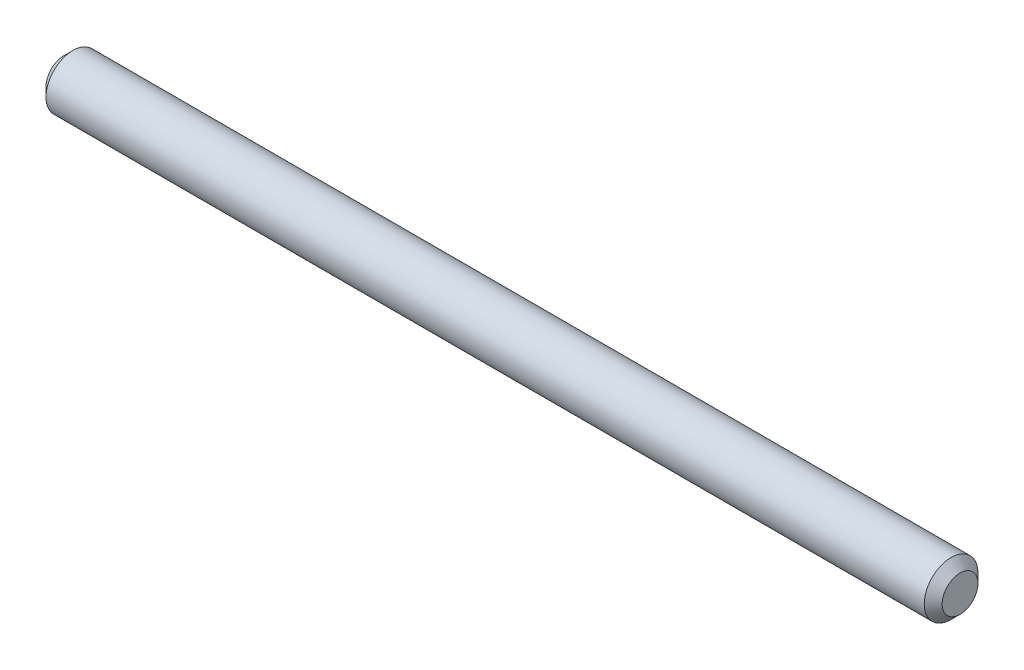
SolidWorks part; units mm, degrees
ref_plane "Front Plane" through (0, 0, 0) normal (0, 0, 1) x (1, 0, 0)
ref_plane "Top Plane" through (0, 0, 0) normal (0, 1, 0) x (1, 0, 0)
ref_plane "Right Plane" through (0, 0, 0) normal (1, 0, 0) x (0, 0, -1)
sketch "Sketch1" plane through (0, 0, 0) normal (0, 0, 1) x (1, 0, 0)
  line L0 (0, 0) -> (50, 0) construction
  line L1 (0, 0) -> (50, 0)
  line L2 (50, 0) -> (50, 1.5)
  line L3 (50, 1.5) -> (0, 1.5)
  line L4 (0, 1.5) -> (0, 0)
  dimension "L" = 50
  dimension "D" = 3
revolve "Revolve1" add sketch "Sketch1" angle 360 about L0
chamfer "Chamfer1" distance 0.5 angle 45 2 edges at (50, 0, 1.5) (0, 0, 1.5)
ref_plane "Plane1" through (0, 0, 1.5) normal (0, 0, 1) x (1, 0, 0)
ref_plane "Plane2" through (50, 0, 0) normal (1, 0, 0) x (0, 0, -1)
other "DeleteFace1" [suppressed]
chamfer "Chamfer2" [suppressed] distance 2 angle 45
ref_plane "Dim. KC" [suppressed] through (2, 0, 0) normal (1, 0, 0) x (0, 0, -1)
ref_plane "Plane3" [suppressed] through (2, 0, 0) normal (1, 0, 0) x (0, 0, -1)
ref_plane "Plane4" [suppressed] through (8, 0, 0) normal (1, 0, 0) x (0, 0, -1)
sketch "Sketch2" [suppressed] plane through (0, 0, 4) normal (0, 0, 1) x (1, 0, 0)
  line L0 (2, 0) -> (8, 0) construction
  line L1 (2, 1.5) -> (8, 1.5)
  line L2 (2, 1.5) -> (2, -1.5) construction
  line L3 (2, -1.5) -> (8, -1.5)
  line L4 (8, 1.5) -> (8, -1.5) construction
  line L5 (5, 1.5) -> (5, -1.5) construction
  line L6 (2, -4.4) -> (2, 4.4) construction
  line L7 (8, 1.5) -> (8, -1.5)
  line L8 (8, -4.4) -> (8, 4.4) construction
  line L9 (2, 1.5) -> (2, -1.5)
  line L12 (2, -4.4) -> (2, 4.4) construction
  dimension "A" = 6
  dimension "B_s" = 3
extrude "Boss-Extrude1" [suppressed] add sketch "Sketch2" against normal blind 1.8 separate body
fillet "Fillet1" [suppressed] type full round
fillet "Fillet2" [suppressed] type full round
sketch "Sketch3" [suppressed] plane through (0, 0, 4) normal (0, 0, 1) x (1, 0, 0)
  line L0 (9, 1.5) -> (9, -1.5) construction
  line L1 (6.5, 1.5) -> (11.5, 1.5)
  line L2 (6.5, 1.5) -> (6.5, -1.5)
  line L3 (6.5, -1.5) -> (11.5, -1.5)
  line L4 (11.5, 1.5) -> (11.5, -1.5)
  line L7 (6.5, 0) -> (11.5, 0) construction
  line L9 (10, 1.5) -> (10, -1.5) construction
  line L10 (8, 1.5) -> (8, -1.5) construction
  line L11 (2, 1.5) -> (8, 1.5) construction
  line L12 (2, -1.5) -> (8, -1.5) construction
  dimension "D1" = 1.5
  dimension "D2" = 2
  dimension "D3" = 1.5
extrude "Boss-Extrude2" [suppressed] add sketch "Sketch3" against normal blind 1.8
fillet "Fillet3" [suppressed] radius 0.1
other "DeleteFace2" [suppressed]
other "DeleteFace3" [suppressed]
combine bodies "Combine1" [suppressed] operation type subtract main body 101 bodies to subtract 146
ref_plane "KC_SEC1" [suppressed] through (5, 0, 0) normal (1, 0, 0) x (0, 0, -1)
ref_plane "KC_SEC2" [suppressed] through (9, 0, 0) normal (1, 0, 0) x (0, 0, -1)
ref_plane "Dim. WKC" [suppressed] through (2, 0, 0) normal (1, 0, 0) x (0, 0, -1)
ref_plane "Dim. K" [suppressed] through (20, 0, 0) normal (1, 0, 0) x (0, 0, -1)
ref_plane "Plane5" [suppressed] through (2, 0, 0) normal (1, 0, 0) x (0, 0, -1)
ref_plane "Plane6" [suppressed] through (20, 0, 0) normal (1, 0, 0) x (0, 0, -1)
sketch "Sketch4" [suppressed] plane through (0, 0, 4) normal (0, 0, 1) x (1, 0, 0)
  line L0 (2, 1.5) -> (2, -1.5)
  line L1 (2, 1.5) -> (8, 1.5)
  line L2 (2, 1.5) -> (2, -1.5) construction
  line L3 (2, -1.5) -> (8, -1.5)
  line L4 (8, 1.5) -> (8, -1.5)
  line L5 (2, -4.4) -> (2, 4.4) construction
  line L6 (2, -3.3) -> (2, 3.3) construction
  line L7 (8, 0) -> (2, 0) construction
  line L8 (5, 1.5) -> (5, -1.5) construction
  dimension "C" = 6
  dimension "B_s" = 3
extrude "Boss-Extrude3" [suppressed] add sketch "Sketch4" against normal blind 1.8 separate body
sketch "Sketch5" [suppressed] plane through (0, 0, 4) normal (0, 0, 1) x (1, 0, 0)
  line L0 (0, 0) -> (20, 0) construction
  line L2 (20, -3.3) -> (20, 3.3) construction
  line L4 (20, -3.3) -> (20, 3.3) construction
  line L5 (17, 1.5) -> (17, -1.5) construction
  line L9 (14, 1.5) -> (20, 1.5)
  line L10 (14, 1.5) -> (14, -1.5)
  line L11 (14, -1.5) -> (20, -1.5)
  line L12 (20, 1.5) -> (20, -1.5) construction
  line L13 (20, 1.5) -> (20, -1.5)
  dimension "B_s" = 3
  dimension "E" = 6
extrude "Boss-Extrude4" [suppressed] add sketch "Sketch5" against normal blind 1.8 separate body
sketch "Sketch6" [suppressed] plane through (0, 0, 4) normal (0, 0, 1) x (1, 0, 0)
  line L0 (2, 1.5) -> (8, 1.5) construction
  line L1 (6.5, 1.5) -> (11.5, 1.5)
  line L2 (6.5, 1.5) -> (6.5, -1.5)
  line L3 (6.5, -1.5) -> (11.5, -1.5)
  line L4 (11.5, 1.5) -> (11.5, -1.5)
  line L5 (2, -1.5) -> (8, -1.5) construction
  line L6 (8, 1.5) -> (8, -1.5) construction
  line L7 (9, 1.5) -> (9, -1.5) construction
  line L8 (10, 1.5) -> (10, -1.5) construction
  dimension "D1" = 1.5
  dimension "D2" = 2
  dimension "D3" = 1.5
extrude "Boss-Extrude5" [suppressed] add sketch "Sketch6" against normal blind 1.8
fillet "Fillet4" [suppressed] type full round
fillet "Fillet5" [suppressed] type full round
fillet "Fillet6" [suppressed] radius 0.1
fillet "Fillet7" [suppressed] type full round
fillet "Fillet8" [suppressed] type full round
fillet "Fillet9" [suppressed] radius 0.1
other "DeleteFace4" [suppressed]
other "DeleteFace5" [suppressed]
other "DeleteFace6" [suppressed]
other "DeleteFace7" [suppressed]
combine bodies "Combine2" [suppressed] operation type subtract main body 101 bodies to subtract 149 135
ref_plane "WKC_SEC1" [suppressed] through (5, 0, 0) normal (1, 0, 0) x (0, 0, -1)
ref_plane "WKC_SEC2" [suppressed] through (17, 0, 0) normal (1, 0, 0) x (0, 0, -1)
ref_plane "WKC_SEC3" [suppressed] through (9, 0, 0) normal (1, 0, 0) x (0, 0, -1)
ref_plane "Dim. KZ" [suppressed] through (2, 0, 0) normal (1, 0, 0) x (0, 0, -1)
ref_plane "Plane7" [suppressed] through (2, 0, 0) normal (1, 0, 0) x (0, 0, -1)
ref_plane "Plane8" [suppressed] through (8, 0, 0) normal (1, 0, 0) x (0, 0, -1)
sketch "Sketch7" [suppressed] plane through (0, 0, 4) normal (0, 0, 1) x (1, 0, 0)
  line L0 (0, 0) -> (8, 0) construction
  line L1 (2, 1.5) -> (8, 1.5)
  line L2 (2, 1.5) -> (2, -1.5) construction
  line L3 (2, -1.5) -> (8, -1.5)
  line L4 (8, 1.5) -> (8, -1.5) construction
  line L5 (2, -4.4) -> (2, 4.4) construction
  line L6 (2, -4.4) -> (2, 4.4) construction
  line L7 (2, 1.5) -> (2, -1.5)
  line L8 (8, 1.5) -> (8, -1.5)
  line L9 (8, -4.4) -> (8, 4.4) construction
  line L10 (5, 1.5) -> (5, -1.5) construction
  dimension "B_s" = 3
  dimension "Z" = 6
extrude "Boss-Extrude6" [suppressed] add sketch "Sketch7" against normal blind 1.8 separate body
fillet "Fillet10" [suppressed] type full round
fillet "Fillet11" [suppressed] type full round
sketch "Sketch8" [suppressed] plane through (0, 0, 4) normal (0, 0, 1) x (1, 0, 0)
  line L0 (1, 1.5) -> (1, -1.5) construction
  line L1 (-1.5, 1.5) -> (3.5, 1.5)
  line L2 (-1.5, 1.5) -> (-1.5, -1.5)
  line L3 (-1.5, -1.5) -> (3.5, -1.5)
  line L4 (3.5, 1.5) -> (3.5, -1.5)
  line L5 (2, 1.5) -> (2, -1.5) construction
  line L7 (-1.5, 0) -> (3.5, 0) construction
  line L9 (0, 1.5) -> (0, -1.5) construction
  line L10 (2, 1.5) -> (8, 1.5) construction
  line L11 (2, -1.5) -> (8, -1.5) construction
  dimension "D1" = 1.5
  dimension "D2" = 2
  dimension "D3" = 1.5
extrude "Boss-Extrude7" [suppressed] add sketch "Sketch8" against normal blind 1.8
fillet "Fillet12" [suppressed] radius 0.1
other "DeleteFace8" [suppressed]
other "DeleteFace9" [suppressed]
combine bodies "Combine3" [suppressed] operation type subtract main body 101 bodies to subtract 147
ref_plane "KZ_SEC1" [suppressed] through (5, 0, 0) normal (1, 0, 0) x (0, 0, -1)
ref_plane "KZ_SEC2" [suppressed] through (1, 0, 0) normal (1, 0, 0) x (0, 0, -1)
ref_plane "Dim. FC" [suppressed] through (1, 0, 0) normal (1, 0, 0) x (0, 0, -1)
sketch "Sketch9" [suppressed] plane through (0, 0, 0) normal (0, 1, 0) x (1, 0, 0)
  line L0 (0, 0) -> (2, 0) construction
  line L1 (1, -3) -> (2, -3)
  line L2 (1, -3) -> (1, -4)
  line L3 (1, -4) -> (2, -4)
  line L4 (2, -3) -> (2, -4)
  line L5 (1, -3.3) -> (1, 3.3) construction
  line L6 (1.5, -4) -> (1.5, -3) construction
  dimension "G" = 1
  dimension "H" = 1
  dimension "D" = 3
extrude "Cut-Extrude1" [suppressed] cut sketch "Sketch9" against normal through all and the other way through all
ref_plane "FC_SEC" [suppressed] through (1.5, 0, 0) normal (1, 0, 0) x (0, 0, -1)
ref_plane "Dim. WFC" [suppressed] through (1, 0, 0) normal (1, 0, 0) x (0, 0, -1)
ref_plane "Dim. W" [suppressed] through (19, 0, 0) normal (1, 0, 0) x (0, 0, -1)
sketch "Sketch10" [suppressed] plane through (0, 0, 0) normal (0, 1, 0) x (1, 0, 0)
  line L0 (0, 0) -> (19, 0) construction
  line L1 (1, -4) -> (2, -4)
  line L2 (1, -4) -> (1, -3)
  line L3 (1, -3) -> (2, -3)
  line L4 (2, -4) -> (2, -3)
  line L5 (1.5, -3) -> (1.5, -4) construction
  line L6 (19, -4) -> (18, -4)
  line L7 (19, -4) -> (19, -3)
  line L8 (19, -3) -> (18, -3)
  line L9 (18, -4) -> (18, -3)
  line L10 (1, -3.3) -> (1, 3.3) construction
  line L11 (19, -3.3) -> (19, 3.3) construction
  line L12 (18.5, -3) -> (18.5, -4) construction
  dimension "J" = 1
  dimension "V" = 1
  dimension "H" = 1
  dimension "D" = 3
  dimension "H_s_R" = 1
extrude "Cut-Extrude2" [suppressed] cut sketch "Sketch10" against normal through all and the other way through all
ref_plane "WFC_SEC1" [suppressed] through (1.5, 0, 0) normal (1, 0, 0) x (0, 0, -1)
ref_plane "WFC_SEC2" [suppressed] through (18.5, 0, 0) normal (1, 0, 0) x (0, 0, -1)
ref_plane "Dim. SFC" [suppressed] through (1, 0, 0) normal (1, 0, 0) x (0, 0, -1)
sketch "Sketch11" [suppressed] plane through (0, 0, 0) normal (0, 1, 0) x (1, 0, 0)
  line L0 (0, 0) -> (2, 0) construction
  line L1 (1, -4) -> (2, -4)
  line L2 (1, -4) -> (1, -3)
  line L3 (1, -3) -> (2, -3)
  line L4 (2, -4) -> (2, -3)
  line L5 (1, -3.3) -> (1, 3.3) construction
  line L6 (1.5, -3) -> (1.5, -4) construction
  dimension "SG" = 1
  dimension "H" = 1
  dimension "D" = 3
extrude "Cut-Extrude3" [suppressed] cut sketch "Sketch11" against normal through all and the other way through all
pattern_circular "CirPattern1" [suppressed] count 2 every 120 of bodies 119
ref_plane "Plane9" [suppressed] through (0, 0, 0) normal (0, -0.5, 0.866) x (1, 0, 0)
sketch "Sketch12" [suppressed] plane through (0, 0, 0) normal (0, -0.5, 0.866) x (1, 0, 0)
  line L0 (0, 0) -> (2, 0) construction
  line L2 (1, -3) -> (2, -3)
  line L3 (1, -3) -> (1, -4)
  line L4 (1, -4) -> (2, -4)
  line L5 (2, -3) -> (2, -4)
  line L6 (1, -3.3) -> (1, 3.3) construction
  dimension "D" = 3
  dimension "SG" = 1
  dimension "H" = 1
ref_plane "SFC_SEC" [suppressed] through (1.5, 0, 0) normal (1, 0, 0) x (0, 0, -1)
sketch "Sketch13" [suppressed] plane through (1.5, 0, 0) normal (1, 0, 0) x (0, 0, -1)
  line L0 (-4, 0) -> (-3, 0) construction
  line L1 (-3, 0) -> (-4, 0) construction
  line L2 (2, -3.4641) -> (1.5, -2.5981) construction
  line L3 (1.5, -2.5981) -> (2, -3.4641) construction
  line L4 (1.5, -2.5981) -> (2, -3.4641) construction
  dimension "ANG" = 120
sketch "Sketch14" [suppressed] plane through (0, 0, 0) normal (0, 1, 0) x (1, 0, 0)
  line L0 (0, 0) -> (20, 0) construction
  line L1 (1.5, 4) -> (1.5, 3.5) construction
  line L2 (0, 3.5) -> (3, 3.5)
  line L3 (0, 3.5) -> (0, 4)
  line L4 (0, 4) -> (3, 4)
  line L5 (3, 3.5) -> (3, 4)
  line L6 (17, 3.5) -> (20, 3.5)
  line L7 (17, 3.5) -> (17, 4)
  line L8 (17, 4) -> (20, 4)
  line L9 (20, 3.5) -> (20, 4)
  line L10 (0, -4) -> (3, -4)
  line L11 (0, -4) -> (0, -3.5)
  line L12 (0, -3.5) -> (3, -3.5)
  line L13 (3, -4) -> (3, -3.5)
  line L14 (17, -4) -> (20, -4)
  line L15 (17, -4) -> (17, -3.5)
  line L16 (17, -3.5) -> (20, -3.5)
  line L17 (20, -4) -> (20, -3.5)
  line L18 (1.5, -3.5) -> (1.5, -4) construction
  line L19 (18.5, 4) -> (18.5, 3.5) construction
  line L20 (18.5, -3.5) -> (18.5, -4) construction
  dimension "D" = 3
  dimension "W_1" = 7
  dimension "KWC" = 3
  dimension "KWC_L1" = 3
  dimension "KWC_R1" = 3
  dimension "KWC_R2" = 3
  dimension "W_1_R" = 7
extrude "Cut-Extrude4" [suppressed] cut sketch "Sketch14" against normal through all and the other way through all
ref_plane "KWC_SEC1" [suppressed] through (1.5, 0, 0) normal (1, 0, 0) x (0, 0, -1)
ref_plane "KWC_SEC2" [suppressed] through (18.5, 0, 0) normal (1, 0, 0) x (0, 0, -1)
sketch "Sketch15" [suppressed] plane through (0, 0, 0) normal (0, 1, 0) x (1, 0, 0)
  line L0 (0, 0) -> (20, 0) construction
  line L1 (1.5, -3) -> (1.5, -4) construction
  line L2 (0, 3) -> (3, 3)
  line L3 (0, 3) -> (0, 4)
  line L4 (0, 4) -> (3, 4)
  line L5 (3, 3) -> (3, 4)
  line L6 (17, 3) -> (20, 3)
  line L7 (17, 3) -> (17, 4)
  line L8 (17, 4) -> (20, 4)
  line L9 (20, 3) -> (20, 4)
  line L10 (0, -4) -> (3, -4)
  line L11 (0, -4) -> (0, -3)
  line L12 (0, -3) -> (3, -3)
  line L13 (3, -4) -> (3, -3)
  line L14 (17, -4) -> (20, -4)
  line L15 (17, -4) -> (17, -3)
  line L16 (17, -3) -> (20, -3)
  line L17 (20, -4) -> (20, -3)
  line L18 (18.5, -3) -> (18.5, -4) construction
  dimension "D" = 3
  dimension "KWC_L1" = 3
  dimension "KWC_R1" = 3
  dimension "WC" = 6
  dimension "KWC" = 3
  dimension "KWC_R2" = 3
  dimension "WC_R" = 6
extrude "Cut-Extrude5" [suppressed] cut sketch "Sketch15" against normal through all and the other way through all
ref_plane "WC_SEC1" [suppressed] through (1.5, 0, 0) normal (1, 0, 0) x (0, 0, -1)
ref_plane "WC_SEC2" [suppressed] through (18.5, 0, 0) normal (1, 0, 0) x (0, 0, -1)
sketch "Sketch16" [suppressed] plane through (0, 0, 0) normal (0, 0, 1) x (1, 0, 0)
  line L0 (20, 4) -> (0, 4) construction
  line L1 (1.1, 3.5) -> (2, 3.5)
  line L2 (1.1, 3.5) -> (1.1, 4)
  line L3 (1.1, 4) -> (2, 4)
  line L4 (2, 3.5) -> (2, 4)
  line L5 (0, 0) -> (2, 0) construction
  line L6 (0, 4) -> (0, 0) construction
  dimension "D_s_1" = 7
  dimension "M_s" = 0.9
  dimension "TA" = 2
revolve "Cut-Revolve1" [suppressed] cut sketch "Sketch16" angle 360 about L5
sketch "Sketch17" [suppressed] plane through (0, 0, 0) normal (0, 0, 1) x (1, 0, 0)
  line L1 (18, 3.5) -> (18.9, 3.5)
  line L2 (18, 3.5) -> (18, 4)
  line L3 (18, 4) -> (18.9, 4)
  line L4 (18.9, 3.5) -> (18.9, 4)
  line L5 (0, 0) -> (20, 0) construction
  line L7 (20, -3.3) -> (20, 3.3) construction
  dimension "D_s_1" = 7
  dimension "M_s" = 0.9
  dimension "D" = 3
  dimension "TB" = 2
revolve "Cut-Revolve2" [suppressed] cut sketch "Sketch17" angle 360 about L5
sketch "Sketch18" [suppressed] plane through (0, 0, 0) normal (0, 0, 1) x (1, 0, 0)
  line L0 (0, 0) -> (20, 0) construction
  line L1 (0, 4) -> (0, -4) construction
  line L3 (1, 4) -> (5, 4)
  line L4 (1, 4) -> (1, 3.5)
  line L5 (1, 3.5) -> (5, 3.5)
  line L6 (5, 4) -> (5, 3.5)
  line L7 (20, 4) -> (0, 4) construction
  line L8 (20, -3.3) -> (20, 3.3) construction
  dimension "D_s_2" = 7
  dimension "UC" = 1
  dimension "L1_s" = 4
revolve "Cut-Revolve3" [suppressed] cut sketch "Sketch18" angle 360 about L0
ref_plane "Dim. SC" [suppressed] through (2, 0, 0) normal (1, 0, 0) x (0, 0, -1)
sketch "Sketch19" [suppressed] plane through (0, 0, 0) normal (0, 1, 0) x (1, 0, 0)
  line L0 (20, -3.3) -> (20, 3.3) construction
  line L1 (2, -3.5) -> (10, -3.5)
  line L2 (2, -3.5) -> (2, -4)
  line L3 (2, -4) -> (10, -4)
  line L4 (10, -3.5) -> (10, -4)
  line L5 (2, 4) -> (10, 4)
  line L6 (2, 4) -> (2, 3.5)
  line L7 (2, 3.5) -> (10, 3.5)
  line L8 (10, 4) -> (10, 3.5)
  line L9 (6, 4) -> (6, 3.5) construction
  line L10 (6, -3.5) -> (6, -4) construction
  line L12 (0, 0) -> (20, 0) construction
  line L14 (2, -3.3) -> (2, 3.3) construction
  dimension "W_2" = 7
  dimension "L2_s" = 8
  dimension "D" = 3
  dimension "L2_s_L1" = 8
extrude "Cut-Extrude6" [suppressed] cut sketch "Sketch19" against normal through all and the other way through all
ref_plane "SC_SEC" [suppressed] through (6, 0, 0) normal (1, 0, 0) x (0, 0, -1)
equation "\"Plane dim\"= \"D@Sketch1\" * 0.5"
equation "\"D1@Plane3\"= if ( \"KC@Dim. KC\" < 1 , 0 , \"KC@Dim. KC\" )"
equation "\"D1@Plane4\" = if ( \"KC@Dim. KC\" > \"L@Sketch1\" - \"A@Sketch2\" - 1 , \"L@Sketch1\" , \"KC@Dim. KC\" + \"A@Sketch2\" )"
equation "\"D1@Plane5\"=if ( \"WKC@Dim. WKC\" < 1 , 0 , \"WKC@Dim. WKC\" )"
equation "\"D1@Plane6\"=if ( \"K@Dim. K\" < 1 , 0 , \"K@Dim. K\" )"
equation "\"D1@Plane7\"=if ( \"KZ@Dim. KZ\" < 1 , 0 , \"KZ@Dim. KZ\" )"
equation "\"D1@Plane8\"=if ( \"KZ@Dim. KZ\" > \"L@Sketch1\" - \"Z@Sketch7\" - 1 , \"L@Sketch1\", \"KZ@Dim. KZ\" + \"Z@Sketch7\" )"
equation "\"D1@Sketch3\"=\"B_s@Sketch2\"/2"
equation "\"D3@Sketch3\"=\"B_s@Sketch2\"/2"
equation "\"D1@Sketch8\"=\"B_s@Sketch7\"/2"
equation "\"D3@Sketch8\"=\"B_s@Sketch7\"/2"
equation "\"D1@Sketch6\"=\"B_s@Sketch4\"/2"
equation "\"D3@Sketch6\"=\"B_s@Sketch4\"/2"
equation "\"D@Sketch12\" = \"D@Sketch11\""
equation "\"SG@Sketch12\" = \"SG@Sketch11\""
equation "\"H@Sketch12\"= \"H@Sketch11\""
